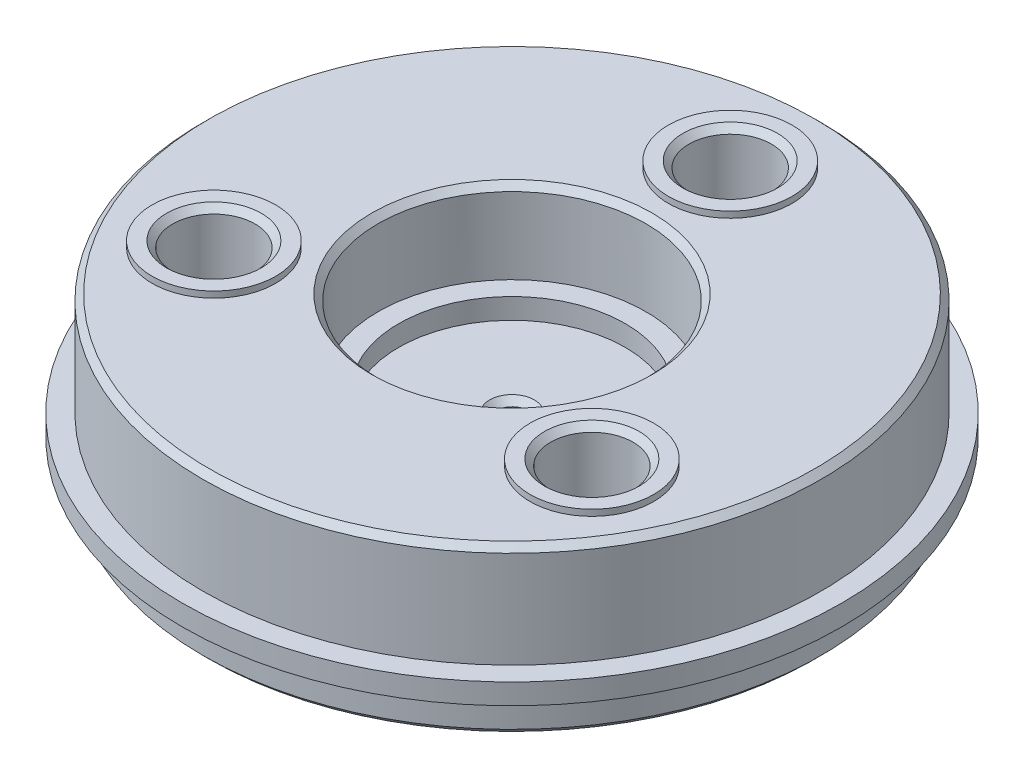
SolidWorks part; units mm, degrees
material "6061 合金"
ref_plane "前视基准面" through (0, 0, 0) normal (0, 0, 1) x (1, 0, 0)
ref_plane "上视基准面" through (0, 0, 0) normal (0, 1, 0) x (1, 0, 0)
ref_plane "右视基准面" through (0, 0, 0) normal (1, 0, 0) x (0, 0, -1)
other "Configuration Table"
sketch "草图1" plane through (0, 0, 0) normal (0, 0, 1) x (1, 0, 0)
  line L0 (0, 0) -> (0, -4.3035) construction
  line L1 (0, -4.3035) -> (0, -7.9699) construction
  line L2 (16, 3) -> (15, 3)
  line L4 (6.5, 8) -> (15, 8)
  line L9 (15, 3) -> (15, 8)
  line L13 (16, 3) -> (16, 2)
  line L16 (0.785, 0) -> (15, 0)
  line L19 (0.785, 3) -> (0.785, 0)
  line L25 (6.5, 8) -> (6.5, 4)
  line L26 (5.5, 4) -> (5.5, 3)
  line L27 (5.5, 3) -> (0.785, 3)
  line L33 (5.5, 4) -> (6.5, 4)
  line L37 (16, 2) -> (15, 2)
  line L38 (15, 0) -> (15, 2)
  dimension "D1" = 30
  dimension "D2" = 5
  dimension "D3" = 1.57
  dimension "D4" = 4
  dimension "D5" = 8
  dimension "D6" = 32
  dimension "D8" = 1
  dimension "D9" = 13
  dimension "D10" = 1
  dimension "D11" = 30
  dimension "D12" = 1
revolve "旋转1" add sketch "草图1" angle 360 about L0
hole_wizard "M3 螺纹孔2" positions "草图6" profile "草图7" tap size "M3" standard "GB"
sketch "草图6" plane through (0, 0, 0) normal (0, 1, 0) x (1, 0, 0)
  line L0 (-12, 0) -> (0, 0) construction
  line L1 (0, 0) -> (-8.0326, 0) construction
  circle A0 centre (0, 0) radius 12 construction
  point P3 (-12, 0)
  dimension "D1" = 24
  dimension "D2" = 0
cosmetic thread "孔螺蚊线4" parameters "D1"=6, "D2"=3
sketch "草图7" plane through (-12, 0, 0) normal (1, 0, 0) x (0, 0, -1)
  line L0 (0, 0) -> (0, 7.5)
  line L1 (0, 7.5) -> (1.25, 6.7489)
  line L2 (1.25, 6.7489) -> (1.25, 0)
  line L5 (1.25, 0) -> (0, 0)
  line L10 (0, 7.5) -> (-1.25, 6.7489) construction
  line L11 (0, -6.35) -> (0, 107.95) construction
  dimension "螺纹孔钻头直径" = 2.5
  dimension "螺纹孔钻头深度" = 7.5
  dimension "导头角度" = 118
pattern_circular "阵列(圆周)2" count 6 over 360 about axis through (0, 0, 0) along (0, 1, 0) of "M3 螺纹孔2" reverse direction yes
sketch "草图8" plane through (0, 8, 0) normal (0, 1, 0) x (1, 0, 0)
  circle A0 centre (0, 10.59) radius 2
  dimension "D2" = 4
  dimension "D1" = 10.59
extrude "切除-拉伸1" cut sketch "草图8" against normal blind 3.7
pattern_circular "阵列(圆周)3" count 3 over 360 about axis through (0, 0, 0) along (0, 1, 0) of "切除-拉伸1"
chamfer "倒角1" distance 0.3 angle 45 3 edges at (0, 8, 15) (0, 8, 6.5) (0, 0, 15)
chamfer "倒角3" distance 0.3 angle 45 1 edges at (0, 3, 0.785)
sketch "草图12" plane through (0, 8, 0) normal (0, 1, 0) x (1, 0, 0)
  circle A0 centre (0, 10.59) radius 3
  circle A1 centre (-9.1712, -5.295) radius 3
  circle A2 centre (9.1712, -5.295) radius 3
  circle A3 centre (9.1712, -5.295) radius 2 construction
  circle A4 centre (-9.1712, -5.295) radius 2 construction
  circle A5 centre (0, 10.59) radius 2 construction
  circle A6 centre (9.1712, -5.295) radius 2
  circle A7 centre (-9.1712, -5.295) radius 2
  circle A8 centre (0, 10.59) radius 2
  dimension "D1" = 6
extrude "凸台-拉伸1" add sketch "草图12" along normal blind 0.3
chamfer "倒角4" distance 0.3 angle 45 3 edges at (9.1712, 8.3, 7.295) (-9.1712, 8.3, 7.295) (0, 8.3, -8.59)
sketch "草图13" plane through (0, 0, 0) normal (0, -1, 0) x (1, 0, 0)
  line L0 (0, 9) -> (0, -9) construction
  line L1 (-3, 6.9282) -> (-3, -6.9282)
  line L2 (3, 6.9282) -> (3, -6.9282)
  line L3 (-3, 9) -> (-3, -9) construction
  line L4 (3, 9) -> (3, -9) construction
  arc A0 (-1.2857, -8.9077) -> (1.2857, -8.9077) centre (0, 0) ccw
  arc A1 (1.2857, 8.9077) -> (-1.2857, 8.9077) centre (0, 0) ccw
  arc A2 (-3, -6.9282) -> (-1.2857, -8.9077) centre (-1, -6.9282) ccw
  arc A3 (1.2857, -8.9077) -> (3, -6.9282) centre (1, -6.9282) ccw
  arc A4 (3, 6.9282) -> (1.2857, 8.9077) centre (1, 6.9282) ccw
  arc A5 (-1.2857, 8.9077) -> (-3, 6.9282) centre (-1, 6.9282) ccw
  circle A6 centre (0, 0) radius 0.785 construction
  circle A7 centre (0, 0) radius 0.785
  point P18 (3, 8.4853)
  dimension "D1" = 18
  dimension "D4" = 2
  dimension "D2" = 3
  dimension "D3" = 3
extrude "凸台-拉伸2" add sketch "草图13" along normal blind 3
chamfer "倒角5" distance 0.3 angle 45 8 edges at (3, -3, 0) (2.5119, -3, 8.2375) (2.5119, -3, -8.2375) (0, -3, 9) (0, -3, -9) (-2.5119, -3, 8.2375) (-2.5119, -3, -8.2375) (-3, -3, 0)
sketch "草图14" plane through (0, 4.3, 0) normal (0, 1, 0) x (1, 0, 0)
  circle A0 centre (9.1712, -5.295) radius 0.75
  circle A1 centre (0, 10.59) radius 0.75
  circle A2 centre (-9.1712, -5.295) radius 0.75
  dimension "D1" = 1.5
extrude "切除-拉伸2" cut sketch "草图14" against normal through all
